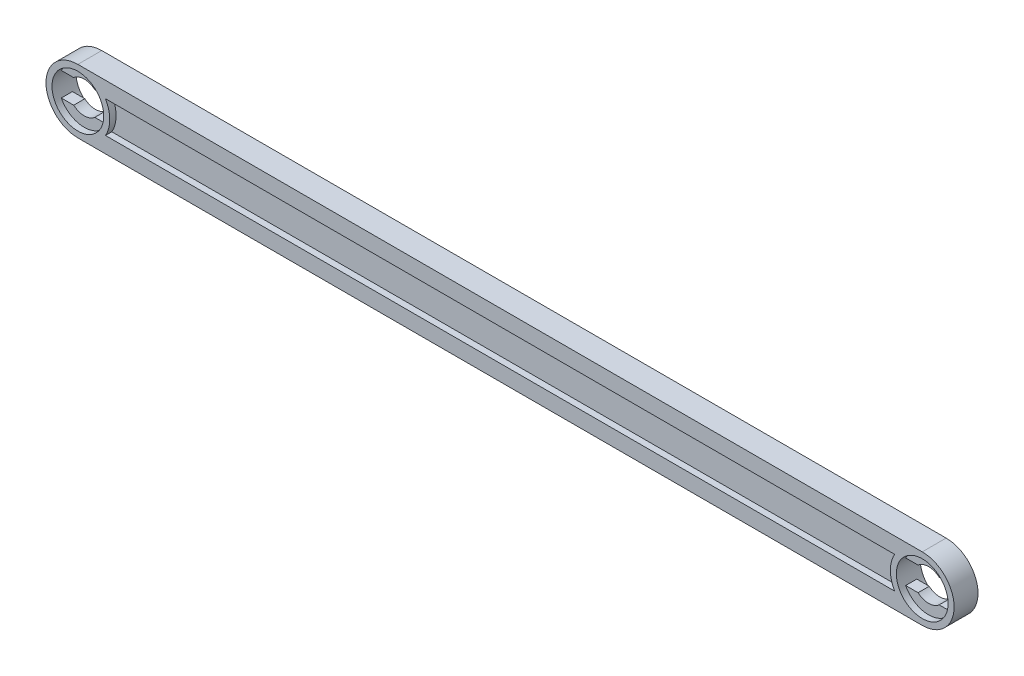
SolidWorks part; units mm, degrees
ref_plane "前视基准面" through (0, 0, 0) normal (0, 0, 1) x (1, 0, 0)
ref_plane "上视基准面" through (0, 0, 0) normal (0, 1, 0) x (1, 0, 0)
ref_plane "右视基准面" through (0, 0, 0) normal (1, 0, 0) x (0, 0, -1)
sketch "草图1" plane through (0, 0, 0) normal (0, 0, 1) x (1, 0, 0)
  line L1 (0, 4) -> (106, 4)
  line L3 (0, -4) -> (106, -4)
  arc A0 (0, 4) -> (0, -4) centre (0, 0) ccw
  arc A1 (106, -4) -> (106, 4) centre (106, 0) ccw
  dimension "D1" = 106
  dimension "D2" = 4
  dimension "D4" = 4
  dimension "D3" = 106
extrude "凸台-拉伸1" add sketch "草图1" against normal blind 3
sketch "草图2" plane through (0, 0, 0) normal (0, 0, 1) x (1, 0, 0)
  line L0 (1.3229, -1.5) -> (2.8831, -1.5)
  line L1 (-2.8831, -1.5) -> (-1.3229, -1.5)
  line L2 (1.3229, 1.5) -> (2.8831, 1.5)
  line L3 (-2.8831, 1.5) -> (-1.3229, 1.5)
  arc A0 (1.3229, 1.5) -> (-1.3229, 1.5) centre (0, 0) ccw
  arc A1 (-2.8831, 1.5) -> (-2.8831, -1.5) centre (0, 0) ccw
  arc A3 (2.8831, -1.5) -> (2.8831, 1.5) centre (0, 0) ccw
  arc A4 (-1.3229, -1.5) -> (1.3229, -1.5) centre (0, 0) ccw
extrude "切除-拉伸1" cut sketch "草图2" against normal up to next
sketch "草图3" plane through (0, 0, 0) normal (0, 0, 1) x (1, 0, 0)
  circle A1 centre (0, 0) radius 3.25
extrude "切除-拉伸2" cut sketch "草图3" against normal blind 0.8
extrude "切除-拉伸3" cut sketch "草图3<2>" along normal blind 0.8 from offset 3 offset against normal yes
sketch "草图3<2>" plane through (0, 0, 0) normal (0, 0, 1) x (1, 0, 0) same geometry as "草图3"
pattern_linear "阵列(线性)1" count 2 spacing 106 along (1, 0, 0) of "切除-拉伸1", "切除-拉伸2", "切除-拉伸3"
sketch "草图4" plane through (0, 0, 0) normal (0, 0, 1) x (1, 0, 0)
  line L0 (0, 0) -> (0, 2) construction
  line L1 (0, 0) -> (0, -2) construction
  line L2 (0, 2) -> (3.4641, 2) construction
  line L3 (0, -2) -> (3.4641, -2) construction
  line L4 (106, 0) -> (106, 2) construction
  line L5 (106, 2) -> (102.5359, 2) construction
  line L6 (106, 0) -> (106, -2) construction
  line L7 (106, -2) -> (102.5359, -2) construction
  line L8 (3.4641, 2) -> (102.5359, 2)
  line L9 (3.4641, -2) -> (102.5359, -2)
  arc A0 (1.3229, 1.5) -> (-1.3229, 1.5) centre (0, 0) ccw construction
  arc A1 (-1.3229, -1.5) -> (1.3229, -1.5) centre (0, 0) ccw construction
  arc A2 (3.4641, -2) -> (3.4641, 2) centre (0, 0) ccw
  arc A3 (102.5359, 2) -> (102.5359, -2) centre (106, 0) ccw
  arc A4 (107.3229, 1.5) -> (104.6771, 1.5) centre (106, 0) ccw construction
  arc A5 (104.6771, -1.5) -> (107.3229, -1.5) centre (106, 0) ccw construction
extrude "切除-拉伸4" cut sketch "草图4" against normal blind 0.8
sketch "草图5" plane through (0, 0, -3) normal (0, 0, -1) x (-1, 0, 0)
  line L0 (-102, -2) -> (-102, 2)
  line L1 (-4, -2) -> (-4, 2)
  line L2 (-102, 2) -> (-4, 2)
  line L3 (-102, 0) -> (-4, 0) construction
  line L4 (-102, -2) -> (-4, -2)
  circle A0 centre (-106, 0) radius 4 construction
  circle A1 centre (0, 0) radius 4 construction
  dimension "D1" = 2
  dimension "D2" = 2
extrude "切除-拉伸5" cut sketch "草图5" against normal blind 0.8
